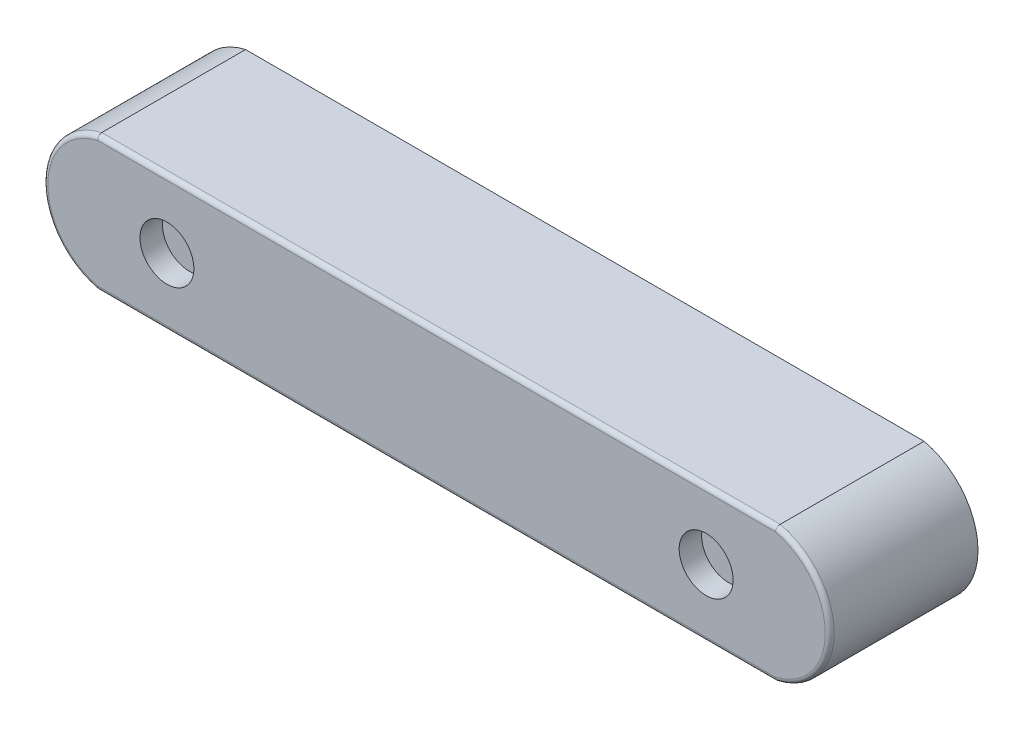
SolidWorks part; units mm, degrees
ref_plane "Front Plane" through (0, 0, 0) normal (0, 0, 1) x (1, 0, 0)
ref_plane "Top Plane" through (0, 0, 0) normal (0, 1, 0) x (1, 0, 0)
ref_plane "Right Plane" through (0, 0, 0) normal (1, 0, 0) x (0, 0, -1)
sketch "Schizzo1" plane through (0, 0, 0) normal (0, 0, 1) x (1, 0, 0)
  line L0 (-75.5, -15) -> (75.5, -15)
  line L1 (-75.5, 15) -> (75.5, 15)
  line L2 (-87.5, 15) -> (-87.5, -15) construction
  line L3 (87.5, 15) -> (87.5, -15) construction
  line L4 (-87.5, -15) -> (87.5, -15) construction
  line L5 (-75.5, 15) -> (-75.5, -15) construction
  line L6 (-87.5, 15) -> (87.5, 15) construction
  line L7 (-75.5, 15) -> (75.5, -15) construction
  arc A0 (-75.5, 15) -> (-75.5, -15) centre (-72.125, 0) ccw
  arc A1 (75.5, 15) -> (75.5, -15) centre (72.125, 0) cw
  point P10 (0, -15)
  point P11 (0, -15)
  point P12 (0, 0)
  dimension "D1" = 151
  dimension "D3" = 175
  dimension "D4" = 30
extrude "Estrusione-Estrusione1" add sketch "Schizzo1" along normal blind 33
fillet "Raccordo1" radius 1 4 edges at (0, 15, 33) (87.5, 0, 33) (0, -15, 33) (-87.5, 0, 33)
sketch "Schizzo2" plane through (0, 0, 33) normal (0, 0, 1) x (1, 0, 0)
  line L0 (-86.5, 0) -> (86.5, 0) construction
  circle A0 centre (-60, 0) radius 6
  circle A1 centre (60, 0) radius 6
  arc A2 (-75.387, 14) -> (-75.387, -14) centre (-72.125, 0) ccw construction
  arc A3 (75.387, -14) -> (75.387, 14) centre (72.125, 0) ccw construction
  dimension "D1" = 12
  dimension "D2" = 12
  dimension "D3" = 120
  dimension "D4" = 60
extrude "Taglio-Estrusione1" cut sketch "Schizzo2" against normal blind 5
sketch "Schizzo3" plane through (0, -15, 0) normal (0, -1, 0) x (1, 0, 0)
  line L0 (-75.5, 0) -> (75.5, 0) construction
  circle A0 centre (0, 15.6) radius 4.46
  dimension "D1" = 8.92
  dimension "D2" = 15.6
  dimension "D3" = 87.5
extrude "Taglio-Estrusione2" cut sketch "Schizzo3" against normal blind 2
sketch "Schizzo4" plane through (0, -13, 0) normal (0, -1, 0) x (1, 0, 0)
  circle A0 centre (0, 15.6) radius 2.65
  dimension "D1" = 5.3
extrude "Taglio-Estrusione3" cut sketch "Schizzo4" against normal blind 8
sketch "Schizzo5" plane through (0, 0, 0) normal (0, 0, -1) x (-1, 0, 0)
  line L0 (0, -10) -> (0, -15) construction
  line L1 (75.5, -15) -> (-75.5, -15) construction
  circle A0 centre (0, -10) radius 2
  dimension "D1" = 4
  dimension "D2" = 5
extrude "Estrusione-Estrusione2" add sketch "Schizzo5" along normal blind 5
